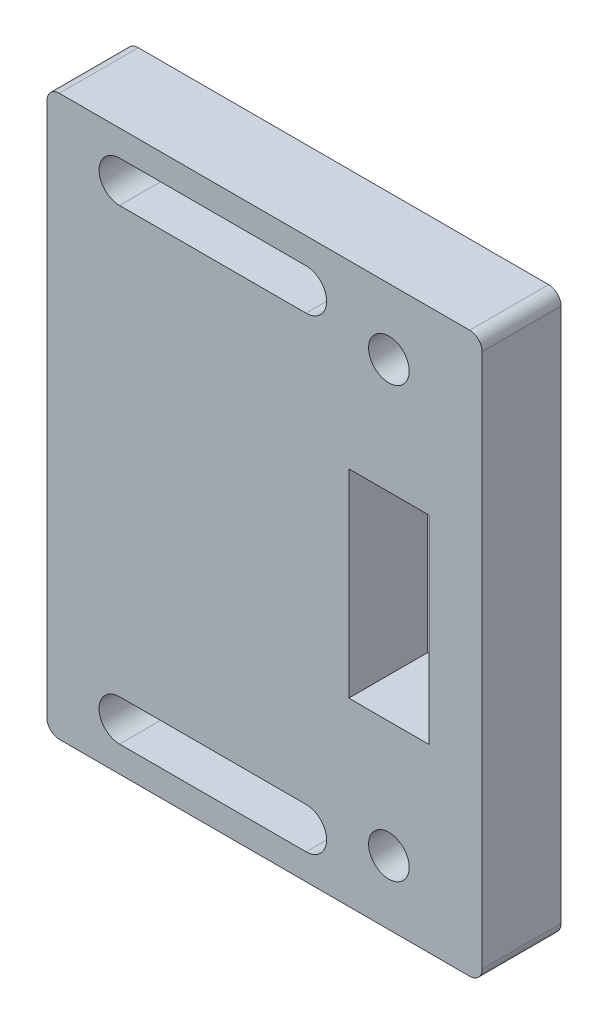
SolidWorks part; units mm, degrees
ref_plane "Front Plane" through (0, 0, 0) normal (0, 0, 1) x (1, 0, 0)
ref_plane "Top Plane" through (0, 0, 0) normal (0, 1, 0) x (1, 0, 0)
ref_plane "Right Plane" through (0, 0, 0) normal (1, 0, 0) x (0, 0, -1)
sketch "Sketch1" plane through (0, 0, 0) normal (0, 0, 1) x (1, 0, 0)
  line L0 (70, -45) -> (0, -45) construction
  line L1 (0, 0) -> (70, 0)
  line L2 (0, 0) -> (0, -90)
  line L3 (0, -90) -> (70, -90)
  line L4 (70, 0) -> (70, -90)
  line L5 (55, -45) -> (55, -29.025) construction
  line L6 (55, -29.025) -> (61.45, -29.025)
  line L7 (61.45, -29.025) -> (61.45, -60.975)
  line L8 (61.45, -60.975) -> (55, -60.975)
  line L9 (55, -60.975) -> (48.55, -60.975)
  line L10 (48.55, -60.975) -> (48.55, -29.025)
  line L11 (48.55, -29.025) -> (55, -29.025)
  line L12 (55, -45) -> (55, -60.975) construction
  line L13 (55, 0) -> (55, -13.25) construction
  line L14 (55, -90) -> (55, -79.56) construction
  dimension "D1" = 90
  dimension "D2" = 55
  dimension "D3" = 12.9
  dimension "D4" = 31.95
  dimension "D5" = 70
  dimension "D6" = 10.44
  dimension "D7" = 55
  dimension "D8" = 55
extrude "Boss-Extrude1" add sketch "Sketch1" along normal blind 12.7
sketch "Sketch4" plane through (0, 0, 0) normal (0, 0, -1) x (-1, 0, 0)
  line L0 (-55, -0.2792) -> (-55, -10.5796)
  line L2 (-55, -90) -> (-55, -79.6996)
  line L4 (-55, -79.6996) -> (-55, -10.5796) construction
  line L5 (0, 0) -> (0, -90) construction
  line L6 (0, -90) -> (-70, -90) construction
  line L9 (0, -90) -> (-70, -90) construction
  dimension "D1" = 55
  dimension "D2" = 10.3004
  dimension "D3" = 69.12
hole_wizard "CSK for 1/4 Flat Head Machine Screw1" positions "Sketch5" profile "Sketch6" countersink size "1/4" standard "ANSI Inch" end condition through all
sketch "Sketch5" plane through (0, 0, 0) normal (0, 0, -1) x (-1, 0, 0)
  point P0 (-55, -10.5796)
  point P3 (-55, -79.6996)
sketch "Sketch6" plane through (55, -10.5796, 0) normal (1, 0, 0) x (0, 1, 0)
  line L0 (0, 0) -> (0, 12.7)
  line L1 (0, 12.7) -> (3.2639, 12.7)
  line L2 (3.2639, 12.7) -> (3.2639, 3.6524)
  line L3 (3.2639, 3.6524) -> (6.4389, 0)
  line L5 (6.4389, 0) -> (0, 0)
  line L6 (-3.2639, 3.6524) -> (-6.4389, 0) construction
  line L11 (0, -6.35) -> (0, 107.95) construction
  dimension "Thru Hole Dia." = 6.5278
  dimension "Thru Hole Depth" = 12.7
  dimension "Near C'Sink Dia." = 12.8778
  dimension "Near C'Sink Angle" = 82
fillet "Fillet1" radius 2 4 edges at (0, 0, 6.35) (70, 0, 6.35) (0, -90, 6.35) (70, -90, 6.35)
sketch "Sketch7" plane through (0, 0, 0) normal (0, 0, -1) x (-1, 0, 0)
  line L0 (-41.6875, -85.815) -> (-11.6875, -85.815)
  line L1 (-11.6875, -79.215) -> (-41.6875, -79.215)
  line L2 (-11.6875, -79.215) -> (-11.6875, -10.785) construction
  line L3 (-11.6875, -10.785) -> (-41.6875, -10.785)
  line L4 (-11.6875, -4.185) -> (-41.6875, -4.185)
  line L5 (-26.6875, -85.815) -> (-26.6875, -90) construction
  line L6 (-2, -90) -> (-68, -90) construction
  line L7 (-26.6875, -4.185) -> (-26.6875, 0) construction
  line L8 (-70, -45) -> (-43.27, -45) construction
  line L9 (-70, -88) -> (-70, -2) construction
  line L10 (-11.6875, -82.515) -> (0, -82.515) construction
  line L11 (0, -2) -> (0, -88) construction
  line L12 (-68, 0) -> (-2, 0) construction
  line L13 (-11.6875, -7.485) -> (0, -7.485) construction
  arc A0 (-11.6875, -85.815) -> (-11.6875, -79.215) centre (-11.6875, -82.515) ccw
  arc A1 (-41.6875, -79.215) -> (-41.6875, -85.815) centre (-41.6875, -82.515) ccw
  arc A2 (-11.6875, -10.785) -> (-11.6875, -4.185) centre (-11.6875, -7.485) ccw
  arc A3 (-41.6875, -4.185) -> (-41.6875, -10.785) centre (-41.6875, -7.485) ccw
  point P28 (-43.27, -45)
  dimension "D1" = 3.3
  dimension "D4" = 3.3
  dimension "D2" = 30
  dimension "D3" = 68.43
  dimension "D5" = 30
  dimension "D6" = 11.6875
extrude "Cut-Extrude1" cut sketch "Sketch7" against normal through all contours A1 L0 A0 L1 | A3 L3 A2 L4
